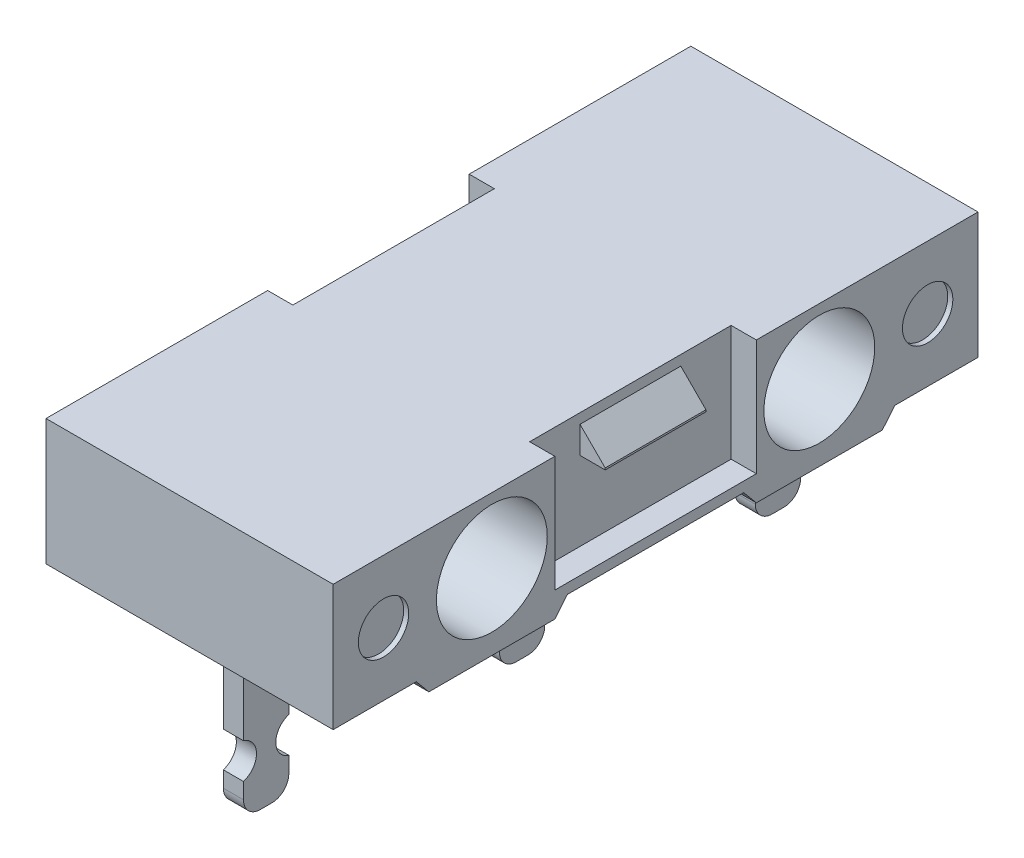
SolidWorks part; units mm, degrees
ref_plane "Спереди" through (0, 0, 0) normal (0, 0, 1) x (1, 0, 0)
ref_plane "Сверху" through (0, 0, 0) normal (0, 1, 0) x (1, 0, 0)
ref_plane "Справа" through (0, 0, 0) normal (1, 0, 0) x (0, 0, -1)
sketch "Эскиз1" plane through (0, 0, 0) normal (1, 0, 0) x (0, 0, -1)
  line L1 (-6.4, -1.25) -> (6.4, -1.25)
  line L2 (-6.4, -1.25) -> (-6.4, 1.25)
  line L3 (-6.4, 1.25) -> (6.4, 1.25)
  line L4 (6.4, -1.25) -> (6.4, 1.25)
  line L5 (-6.4, -1.25) -> (6.4, 1.25) construction
  line L6 (-6.4, 1.25) -> (6.4, -1.25) construction
  point P0 (0, 0)
  dimension "D1" = 12.8
  dimension "D2" = 2.5
extrude "Body" add sketch "Эскиз1" along normal blind 5.7
sketch "Эскиз3" plane through (5.7, 0, 0) normal (1, 0, 0) x (0, 0, -1)
  line L0 (0, 0) -> (0, 1.25) construction
  line L1 (6.4, 1.25) -> (-6.4, 1.25) construction
  line L2 (-4.75, -1.25) -> (-4.5, -1.55)
  line L3 (-6.4, -1.25) -> (6.4, -1.25) construction
  line L4 (-4.5, -1.55) -> (-2, -1.55)
  line L5 (-2, -1.55) -> (-1.75, -1.25)
  line L6 (-1.75, -1.25) -> (-4.75, -1.25)
  line L7 (-3.25, -1.55) -> (-3.25, -1.25) construction
  line L8 (-6.4, 1.25) -> (-6.4, -1.25) construction
  line L9 (2, -1.55) -> (1.75, -1.25)
  line L10 (4.5, -1.55) -> (2, -1.55)
  line L11 (4.75, -1.25) -> (4.5, -1.55)
  line L12 (1.75, -1.25) -> (4.75, -1.25)
  dimension "D1" = 3.15
  dimension "D2" = 2.5
  dimension "D3" = 3
  dimension "D4" = 0.3
extrude "Body_1" add sketch "Эскиз3" against normal up to surface (5.7 mm away) up to face at (0, 0, 0)
sketch "Эскиз4" plane through (5.7, 0, 0) normal (1, 0, 0) x (0, 0, -1)
  line L0 (0, 0) -> (0, 1.25) construction
  line L1 (6.4, 1.25) -> (-6.4, 1.25) construction
  line L2 (-1.75, -1.25) -> (1.75, -1.25) construction
  line L3 (-2, 1.25) -> (2, 1.25)
  line L4 (-2, 1.25) -> (-2, -1.05)
  line L5 (-2, -1.05) -> (2, -1.05)
  line L6 (2, 1.25) -> (2, -1.05)
  line L8 (-1, 0.5149) -> (1, 0.5149)
  line L9 (-1, 0.5149) -> (-1, 1.05)
  line L10 (-1, 1.05) -> (1, 1.05)
  line L11 (1, 0.5149) -> (1, 1.05)
  line L12 (-1, 0.5149) -> (1, 1.05) construction
  line L13 (-1, 1.05) -> (1, 0.5149) construction
  point P11 (0, 0.7825)
  dimension "D1" = 4
  dimension "D2" = 0.2
  dimension "D3" = 1
  dimension "D4" = 0.2
extrude "Cut" cut sketch "Эскиз4" against normal blind 0.5
sketch "Эскиз2" plane through (5.7, 0, 0) normal (1, 0, 0) x (0, 0, -1)
  line L0 (0, 0) -> (0, 1.25) construction
  line L1 (6.4, 1.25) -> (2, 1.25) construction
  line L2 (-4.5, -1.55) -> (-2, -1.55) construction
  circle A0 centre (-3.25, -0.05) radius 1.1
  circle A1 centre (3.25, -0.05) radius 1.1
  dimension "D1" = 2.2
  dimension "D2" = 6.5
  dimension "D3" = 1.5
extrude "Holes" cut sketch "Эскиз2" against normal up to surface (5.7 mm away) up to face at (0, -0.9333, 0)
ref_plane "Plane1" through (2.85, 0, 0) normal (1, 0, 0) x (0, 0, -1)
mirror "Mirror" about plane through (2.85, 0, 0) normal (1, 0, 0) of "Cut"
chamfer "Chamfer" distance 0.5 angle 45 2 edges at (5.7, 1.05, 0) (0, 1.05, 0)
sketch "Эскиз5" plane through (0, -1.25, 0) normal (0, -1, 0) x (1, 0, 0)
  line L0 (2.85, 6.4) -> (2.85, -6.4) construction
  line L1 (5.7, 6.4) -> (0, 6.4) construction
  line L2 (5.7, -6.4) -> (0, -6.4) construction
  line L3 (0, 0) -> (5.7, 0) construction
  line L4 (2.65, 5.53) -> (3.05, 5.53)
  line L5 (2.65, 5.53) -> (2.65, 4.63)
  line L6 (2.65, 4.63) -> (3.05, 4.63)
  line L7 (3.05, 5.53) -> (3.05, 4.63)
  line L8 (2.65, 5.53) -> (3.05, 4.63) construction
  line L9 (2.65, 4.63) -> (3.05, 5.53) construction
  line L10 (5.7, 1.75) -> (5.7, -1.75) construction
  line L11 (2.65, -4.63) -> (3.05, -5.53) construction
  line L12 (2.65, -5.53) -> (3.05, -4.63) construction
  line L13 (3.05, -5.53) -> (3.05, -4.63)
  line L14 (2.65, -4.63) -> (3.05, -4.63)
  line L15 (2.65, -5.53) -> (2.65, -4.63)
  line L16 (2.65, -5.53) -> (3.05, -5.53)
  line L18 (2.65, -0.45) -> (3.05, -0.45)
  line L19 (2.65, -0.45) -> (2.65, 0.45)
  line L20 (2.65, 0.45) -> (3.05, 0.45)
  line L21 (3.05, -0.45) -> (3.05, 0.45)
  line L22 (2.65, -0.45) -> (3.05, 0.45) construction
  line L23 (2.65, 0.45) -> (3.05, -0.45) construction
  point P6 (2.85, 5.08)
  point P20 (2.85, -5.08)
  point P21 (2.85, 0)
  dimension "D1" = 0.4
  dimension "D2" = 0.9
  dimension "D3" = 10.16
extrude "Legs" add sketch "Эскиз5" along normal blind 3.3
sketch "Эскиз6" plane through (3.05, 0, 0) normal (1, 0, 0) x (0, 0, -1)
  line L0 (-5.53, -3.2) -> (-5.53, -3.9)
  line L1 (-5.53, -4.55) -> (-5.53, -1.25) construction
  line L2 (-4.63, -4.55) -> (-5.53, -4.55) construction
  line L3 (-5.08, -4.55) -> (-5.08, -1.25) construction
  line L4 (-6.4, -1.25) -> (-4.75, -1.25) construction
  line L5 (-4.63, -3.2) -> (-4.63, -3.9)
  line L6 (-5.53, -3.55) -> (5.53, -3.55) construction
  line L7 (5.53, -4.55) -> (5.53, -1.25) construction
  line L9 (0.45, -3.2) -> (0.45, -3.9)
  line L10 (-0.45, -4.55) -> (-0.45, -1.25) construction
  line L11 (0.45, -4.55) -> (0.45, -1.25) construction
  line L12 (-0.45, -3.2) -> (-0.45, -3.9)
  line L13 (5.08, -4.55) -> (5.08, -1.25) construction
  line L14 (5.53, -4.55) -> (4.63, -4.55) construction
  line L15 (5.53, -1.25) -> (4.75, -1.25) construction
  line L16 (4.63, -3.2) -> (4.63, -3.9)
  line L17 (4.63, -4.55) -> (4.63, -1.394) construction
  line L18 (5.53, -3.2) -> (5.53, -3.9)
  arc A0 (-5.53, -3.2) -> (-5.53, -3.9) centre (-5.6377, -3.55) cw
  arc A1 (-4.63, -3.2) -> (-4.63, -3.9) centre (-4.5223, -3.55) ccw
  arc A3 (0.45, -3.2) -> (0.45, -3.9) centre (0.5577, -3.55) ccw
  arc A4 (-0.45, -3.2) -> (-0.45, -3.9) centre (-0.5577, -3.55) cw
  arc A5 (4.63, -3.2) -> (4.63, -3.9) centre (4.5223, -3.55) cw
  arc A6 (5.53, -3.2) -> (5.53, -3.9) centre (5.6377, -3.55) ccw
  point P24 (-0.45, -3.55)
  point P32 (0.45, -3.55)
  point P39 (4.63, -3.55)
  dimension "D3" = 0.3662
  dimension "D2" = 1
  dimension "D1" = 0.7
extrude "Вырез-Вытянуть3" cut sketch "Эскиз6" against normal up to surface (0.4 mm away) up to face at (2.65, -2.5988, 5.014)
fillet "Скругление1" radius 0.335 6 edges at (2.85, -4.55, -5.53) (2.85, -4.55, -4.63) (2.85, -4.55, -0.45) (2.85, -4.55, 0.45) (2.85, -4.55, 4.63) (2.85, -4.55, 5.53)
sketch "Эскиз7" plane through (0, 0, 0) normal (-1, 0, 0) x (0, 0, 1)
  line L0 (2, 1.25) -> (6.4, 1.25) construction
  line L1 (-6.0347, -0.6) -> (-4.8347, -0.6)
  line L2 (-6.0347, -0.6) -> (-6.0347, 0.6)
  line L3 (-6.0347, 0.6) -> (-4.8347, 0.6)
  line L4 (-4.8347, -0.6) -> (-4.8347, 0.6)
  line L5 (-6.0347, -0.6) -> (-4.8347, 0.6) construction
  line L6 (-6.0347, 0.6) -> (-4.8347, -0.6) construction
  line L7 (6.4, 1.25) -> (6.4, -1.25) construction
  text T0 "<r-90>5</r>" font "Arial" height 1
  text T1 "<r-90>9</r>" font "Arial" height 1
  point P0 (-5.4347, 0)
  dimension "D1" = 1.2
  dimension "D2" = 0.8
  dimension "D3" = 0.5
  dimension "D4" = 1.3
extrude "Text1" cut sketch "Эскиз7" against normal blind 0.1
sketch "Эскиз8" plane through (5.7, 0, 0) normal (1, 0, 0) x (0, 0, -1)
  line L0 (0, 0) -> (0, 5.5661) construction
  line L1 (-6.4, 1.25) -> (-6.4, -1.25) construction
  circle A0 centre (-5.4, 0) radius 0.5
  circle A1 centre (5.4, 0) radius 0.5
  dimension "D1" = 1
  dimension "D2" = 1
extrude "Circles1" cut sketch "Эскиз8" against normal blind 0.1
